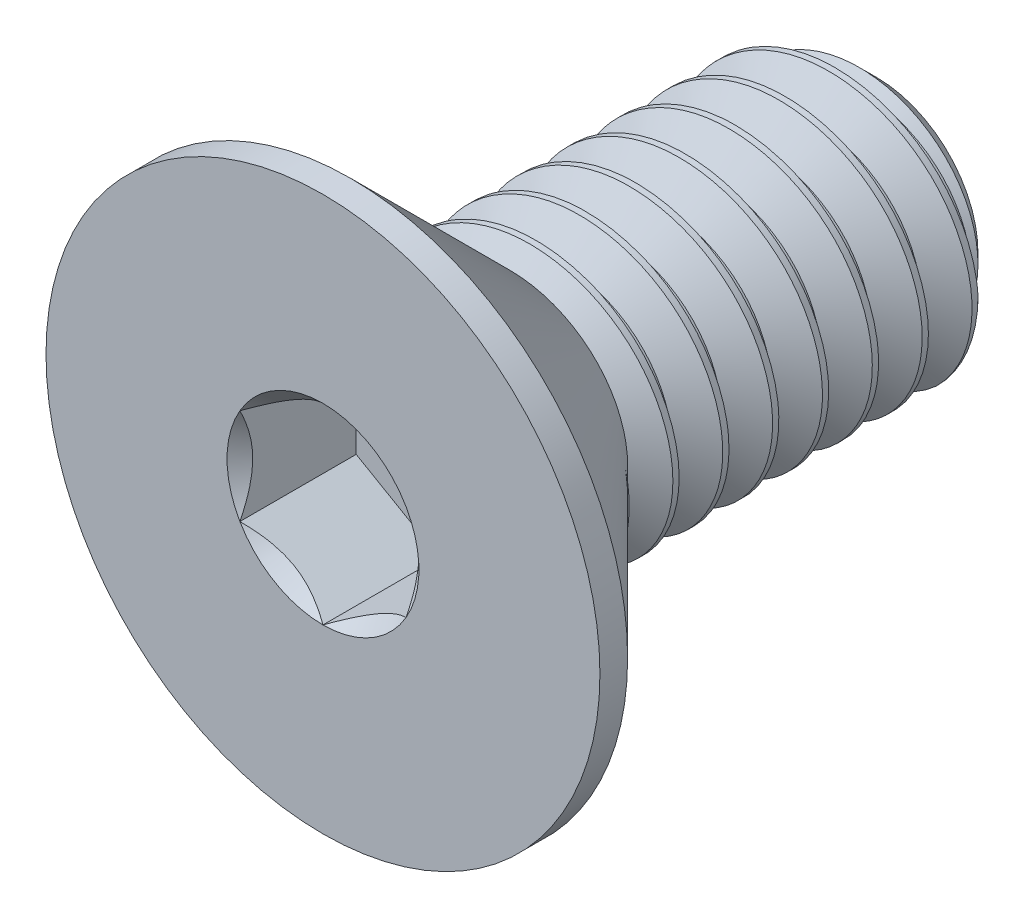
SolidWorks part; units mm, degrees
ref_plane "Front" through (0, 0, 0) normal (0, 0, 1) x (1, 0, 0)
ref_plane "Top" through (0, 0, 0) normal (0, 1, 0) x (1, 0, 0)
ref_plane "Right" through (0, 0, 0) normal (1, 0, 0) x (0, 0, -1)
sketch "Sketch1" plane through (0, 0, 0) normal (1, 0, 0) x (0, 0, -1)
  line L0 (0, 2.5) -> (0.25, 2.5) construction
  line L1 (0.25, 2.5) -> (1.5, 1.25) construction
  line L2 (0, 1.25) -> (5, 1.25)
  line L3 (5, 1.25) -> (5, 0)
  line L4 (5, 0) -> (0, 0)
  line L5 (0, 0) -> (0, 2.5) construction
  line L6 (0, 2.5) -> (0, -2.5) construction
  line L7 (5, 1.25) -> (5, -1.25) construction
  line L8 (0, -2.5) -> (0.25, -2.5) construction
  line L9 (0.25, -2.5) -> (1.5, -1.25) construction
  line L11 (0, 1.25) -> (0, 0)
  line L12 (1.5, 1.25) -> (1.5, 0) construction
revolve "Revolve1" add sketch "Sketch1" angle 360 mid plane about L4
sketch "Sketch3" plane through (0, 0, -5) normal (0, 0, -1) x (-1, 0, 0)
  circle A0 centre (0, 0) radius 1.25
curve "Helix/Spiral1" pitch 0.45 height 5 radius 1.25 centre (0, 0, -5) axis (0, 0, 1) start towards (0, 1, 0)
sketch "Sketch2" plane through (0, 0, 0) normal (1, 0, 0) x (0, 0, -1)
  line L0 (5, 1.25) -> (5.3938, 1.25)
  line L1 (5.3938, 1.25) -> (5.225, 0.9577)
  line L2 (5.225, 0.9577) -> (5.1687, 0.9577)
  line L3 (5.1687, 0.9577) -> (5, 1.25)
  line L4 (5.0844, 1.1039) -> (5.3094, 1.1039) construction
  dimension "D1" = 60
  dimension "D2" = 0.0563
  dimension "D3" = 0.225
chamfer "Chamfer1" distance 0.3375 angle 45 1 edges at (0, 1.25, -5)
sweep "Cut-Sweep1" cut profiles "Sketch2" path "Helix/Spiral1" align with end faces yes
sketch "Sketch7" plane through (0, 0, 0) normal (1, 0, 0) x (0, 0, -1)
  line L0 (0, 2.5) -> (0.25, 2.5) construction
  line L1 (0.25, 2.5) -> (1.5, 1.25) construction
  line L2 (0, 2.5) -> (0.25, 2.5)
  line L3 (0.25, 2.5) -> (1.5, 1.25)
  line L4 (1.5, 1.25) -> (1.5, 0) construction
  line L5 (1.5, 1.25) -> (1.5, 0)
  line L7 (0, 0) -> (0, 2.5) construction
  line L8 (0, 0) -> (0, 2.5)
  line L9 (0, 0) -> (1.5, 0)
  line L10 (2.75, 0) -> (-2.75, 0) construction
revolve "Revolve2" add sketch "Sketch7" angle 360 mid plane about L9
ref_plane "Plane1" through (0, 0, -1.5) normal (0, 0, 1) x (1, 0, 0)
sketch "Sketch8" plane through (0, 0, -1.5) normal (0, 0, 1) x (1, 0, 0)
  circle A0 centre (0, 0) radius 1.25
extrude "Boss-Extrude1" add sketch "Sketch8" against normal through all draft 45
sketch "Sketch5" plane through (0, 0, 0) normal (0, 0, 1) x (1, 0, 0)
  line L1 (0.75, -0.433) -> (0.75, 0.433)
  line L2 (0.75, 0.433) -> (0, 0.866)
  line L3 (0, 0.866) -> (-0.75, 0.433)
  line L4 (-0.75, 0.433) -> (-0.75, -0.433)
  line L5 (-0.75, -0.433) -> (0, -0.866)
  line L6 (0, -0.866) -> (0.75, -0.433)
  circle A0 centre (0, 0) radius 0.75 construction
  dimension "Hex" = 1.5
extrude "Cut-Extrude2" cut sketch "Sketch5" against normal blind 1.05
sketch "Sketch6" plane through (0, 0, 0) normal (0, 0, 1) x (1, 0, 0)
  circle A0 centre (0, 0) radius 0.866
extrude "Cut-Extrude3" cut sketch "Sketch6" against normal blind 1.05 draft 45
sketch "Sketch9" [suppressed] plane through (0, 0, -1.5) normal (0, 0, 1) x (1, 0, 0)
  circle A1 centre (0, 0) radius 1.25
  circle A2 centre (0, 0) radius 1.25
  point P0 (0, 1.25)
  dimension "D1" = 0
extrude "Boss-Extrude2" [suppressed] add sketch "Sketch9" against normal offset from surface (3.5 mm away) 26 up to face at (0, 0.9125, -5)
fillet "Fillet1" [suppressed] radius 0.25
sketch "Sketch10" plane through (0, 0, 0) normal (1, 0, 0) x (0, 0, -1)
  line L0 (5, 1.25) -> (5, -1.25) construction
  point P0 (4.325, -1.25)
  dimension "D1" = 0.675
equation "\"D3@Helix/Spiral1\" = \"Lg@Sketch1\""
equation "\"D2@Sketch2\" = \"D4@Helix/Spiral1\" * .125"
equation "\"D3@Sketch2\" = \"D4@Helix/Spiral1\" * .5"
equation "\"D1@Chamfer1\" = \"D4@Helix/Spiral1\" * .75"
equation "\"D1@Cut-Extrude2\" = \"Head Ht@Sketch1\" * .7"
equation "\"D1@Sketch10\" = \"D4@Helix/Spiral1\" * 1.5"
equation "\"D1@Cut-Extrude3\" = \"D1@Cut-Extrude2\""
equation "\"D1@Fillet1\" = \"Dia@Sketch1\" * .1"
